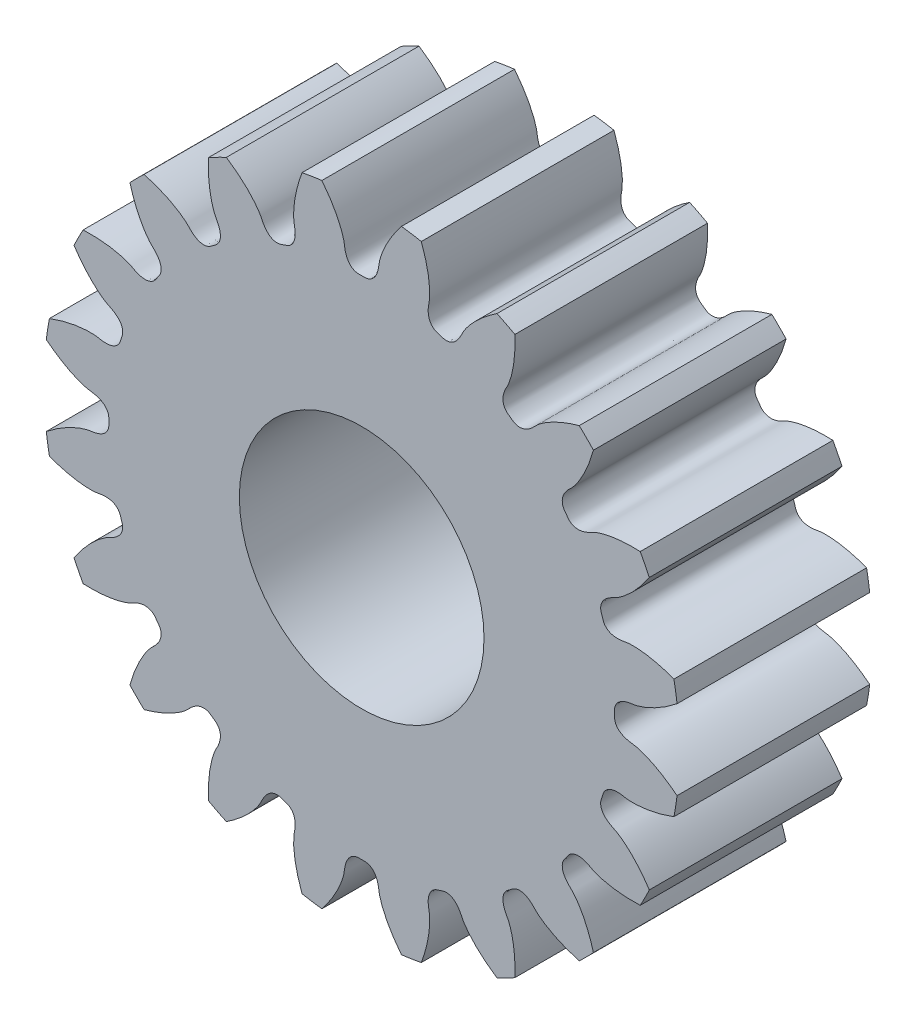
SolidWorks part; units mm, degrees
ref_plane "Front Plane" through (0, 0, 0) normal (0, 0, 1) x (1, 0, 0)
ref_plane "Top Plane" through (0, 0, 0) normal (0, 1, 0) x (1, 0, 0)
ref_plane "Right Plane" through (0, 0, 0) normal (1, 0, 0) x (0, 0, -1)
ref_axis "Axis1" through (0, 0, 55) along (0, 0, -1)
sketch "SketchRevolveSpurAssembly01Pinion" plane through (0, 0, 0) normal (1, 0, 0) x (0, 0, -1)
  line L0 (0, 0) -> (1, 0) construction
  line L1 (-5, 0) -> (-5, 16.5)
  line L2 (-5, 16.5) -> (5, 16.5)
  line L3 (5, 16.5) -> (5, 0)
  line L4 (5, 0) -> (-5, 0)
  dimension "Side1" = 5
  dimension "OutsideRadius" = 16.5
  dimension "Side2" = 5
revolve "SpurAssembly01Pinion" add sketch "SketchRevolveSpurAssembly01Pinion" angle 360 about L0
sketch "SketchToothSpurAssembly01Pinion" plane through (0, 0, 0) normal (0, 0, 1) x (1, 0, 0)
  arc A0 (16.4388, 2.1204) -> (16.4388, -2.1204) centre (0, 0) cw
  spline S0 degree 3 poles (16.4388, -2.1204) (16.3062, -2.0126) (16.1079, -1.8609) (15.8417, -1.6767) (15.6549, -1.5557) (15.4759, -1.4476) (15.3054, -1.3516) (15.1441, -1.2672) (14.9923, -1.1937) (14.8506, -1.1305) (14.7196, -1.0767) (14.5996, -1.0318) (14.491, -0.9949) (14.3942, -0.9653) (14.3096, -0.9423) (14.2375, -0.925) (14.178, -0.9126) (14.0492, -0.8903) (13.9123, -0.8782) (13.7697, -0.8427) (13.6956, -0.8206) (13.6244, -0.795) (13.5557, -0.7654) (13.4893, -0.7311) (13.4248, -0.6913) (13.3623, -0.6446) (13.3021, -0.5892) (13.2452, -0.523) (13.1943, -0.4439) (13.1533, -0.3509) (13.1303, -0.2534) (13.1208, -0.135) (13.1277, 0) (13.1208, 0.135) (13.1303, 0.2534) (13.1533, 0.3509) (13.1943, 0.4439) (13.2452, 0.523) (13.3021, 0.5892) (13.3623, 0.6446) (13.4248, 0.6913) (13.4893, 0.7311) (13.5557, 0.7654) (13.6244, 0.795) (13.6956, 0.8206) (13.7697, 0.8427) (13.9123, 0.8782) (14.0492, 0.8903) (14.178, 0.9126) (14.2375, 0.925) (14.3096, 0.9423) (14.3942, 0.9653) (14.491, 0.9949) (14.5996, 1.0318) (14.7196, 1.0767) (14.8506, 1.1305) (14.9923, 1.1937) (15.1441, 1.2672) (15.3054, 1.3516) (15.4759, 1.4476) (15.6549, 1.5557) (15.8417, 1.6767) (16.1079, 1.8609) (16.3062, 2.0126) (16.4388, 2.1204) knots 0 0 0 0 0.061423 0.08971 0.11638 0.141434 0.164872 0.186693 0.206898 0.225486 0.242459 0.257814 0.271554 0.283677 0.294183 0.303073 0.310347 0.316004 0.350077 0.359568 0.368803 0.377844 0.386769 0.395676 0.404689 0.413963 0.423683 0.434051 0.445256 0.457401 0.47042 0.481067 0.5 0.518933 0.52958 0.542599 0.554744 0.565949 0.576317 0.586037 0.595311 0.604324 0.613231 0.622156 0.631197 0.640432 0.649923 0.683996 0.689653 0.696927 0.705817 0.716323 0.728446 0.742186 0.757541 0.774514 0.793102 0.813307 0.835128 0.858566 0.88362 0.91029 0.938577 1 1 1 1
extrude "ToothExtrudeCutSpurAssembly01Pinion" cut sketch "SketchToothSpurAssembly01Pinion" against normal blind 5 and the other way blind 5
pattern_circular "PatternSpurAssembly01Pinion" count 20 every 18 about axis through (0, 0, 55) along (0, 0, -1) of "ToothExtrudeCutSpurAssembly01Pinion"
sketch "BoreRevolveSketch" plane through (0, 0, 0) normal (1, 0, 0) x (0, 0, -1)
  line L0 (0, 0) -> (1, 0) construction
  line L1 (-5, 0) -> (5, 0)
  line L2 (5, 0) -> (5, 6.35)
  line L3 (5, 6.35) -> (-5, 6.35)
  line L4 (-5, 6.35) -> (-5, 0)
  dimension "BoreSide1" = 5
  dimension "TaperSide1" = 6.35
  dimension "BoreSide2" = 5
  dimension "TaperSide2" = 6.35
revolve "BoreRevolveCut" cut sketch "BoreRevolveSketch" angle 360 about L0
sketch "AuxiliarySketchSpurAssembly01Pinion" plane through (0, 0, 0) normal (0, 0, 1) x (1, 0, 0)
  circle A0 centre (0, 0) radius 15 construction
  circle A1 centre (0, 0) radius 14.0954 construction
  circle A2 centre (0, 0) radius 14.1048 construction
  circle A3 centre (0, 0) radius 16.5 construction
  circle A4 centre (0, 0) radius 13.125 construction
  dimension "PitchDiameter" = 30
  dimension "BaseDiameter" = 28.1908
  dimension "FormDiameter" = 28.2095
  dimension "MajorDiameter" = 33
  dimension "MinorDiameter" = 26.25
